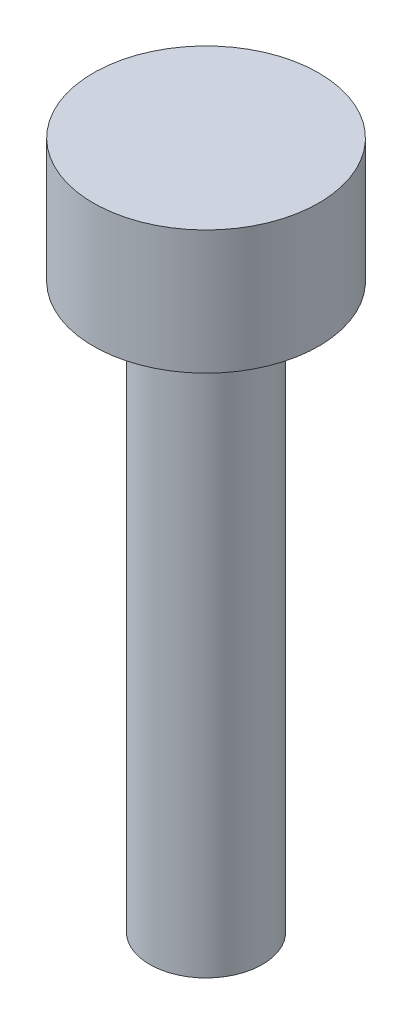
SolidWorks part; units mm, degrees
material "6061-T6 (SS)"
ref_plane "Alzado" through (0, 0, 0) normal (0, 0, 1) x (1, 0, 0)
ref_plane "Planta" through (0, 0, 0) normal (0, 1, 0) x (1, 0, 0)
ref_plane "Vista lateral" through (0, 0, 0) normal (1, 0, 0) x (0, 0, -1)
sketch "Croquis1" plane through (0, 0, 0) normal (0, 0, 1) x (1, 0, 0)
  line L0 (0, 0) -> (-2, 0)
  line L1 (-2, 0) -> (-2, -2.2)
  line L2 (-2, -2.2) -> (-1, -2.2)
  line L3 (-1, -2.2) -> (-1, -12.2)
  line L4 (-1, -12.2) -> (0, -12.2)
  line L5 (0, -12.2) -> (0, 0)
  dimension "D1" = 10
  dimension "D2" = 2
  dimension "D3" = 1
  dimension "D4" = 2.2
revolve "Revolución1" add sketch "Croquis1" angle 360 about L5
